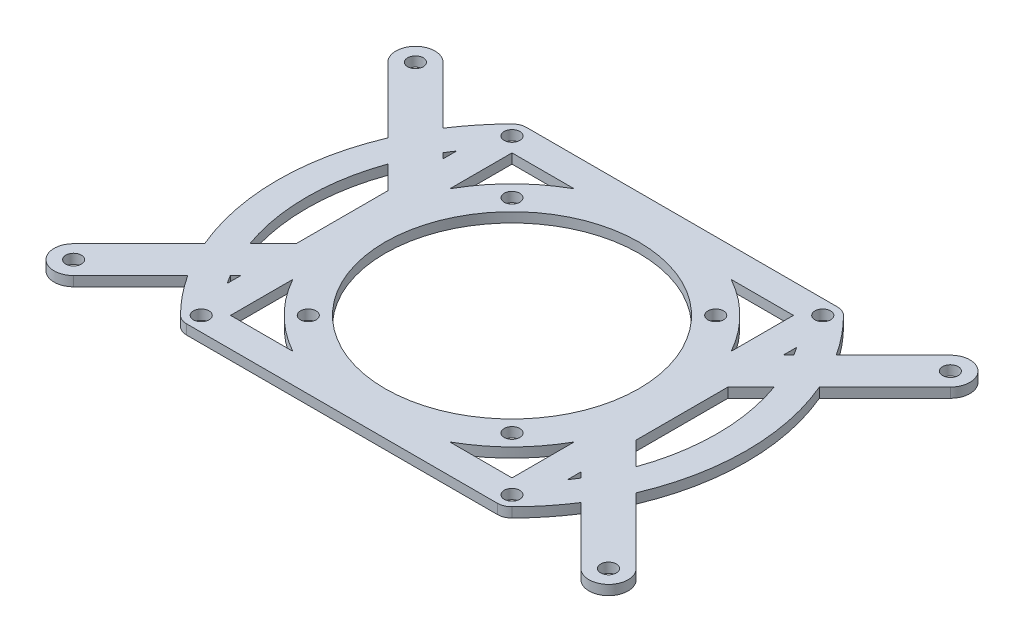
SolidWorks part; units mm, degrees
ref_plane "Front Plane" through (0, 0, 0) normal (0, 0, 1) x (1, 0, 0)
ref_plane "Top Plane" through (0, 0, 0) normal (0, 1, 0) x (1, 0, 0)
ref_plane "Right Plane" through (0, 0, 0) normal (1, 0, 0) x (0, 0, -1)
sketch "Sketch1" plane through (0, 0, 0) normal (0, 1, 0) x (1, 0, 0)
  line L1 (0, 4.2426) -> (-16.1407, 20.3833)
  line L3 (-51.9438, 37.8284) -> (-29.2993, 15.1839)
  line L4 (57.6006, 32.1716) -> (32.2808, 6.8518)
  line L5 (-57.6006, 32.1716) -> (-32.2808, 6.8518)
  line L6 (51.9438, 37.8284) -> (29.2993, 15.1839)
  line L7 (51.9438, -37.8284) -> (29.2993, -15.1839)
  line L8 (57.6006, -32.1716) -> (32.2808, -6.8518)
  line L9 (-57.6006, -32.1716) -> (-32.2808, -6.8518)
  line L10 (-51.9438, -37.8284) -> (-29.2993, -15.1839)
  line L11 (0, 4.2426) -> (16.1407, 20.3833)
  line L13 (0, -4.2426) -> (-16.1407, -20.3833)
  line L15 (0, -4.2426) -> (16.1407, -20.3833)
  line L16 (4.2426, 0) -> (20.3833, -16.1407)
  line L17 (-4.2426, 0) -> (-20.3833, -16.1407)
  line L18 (-4.2426, 0) -> (-20.3833, 16.1407)
  line L19 (4.2426, 0) -> (20.3833, 16.1407)
  circle A0 centre (54.7722, 35) radius 1.6
  arc A1 (57.6006, 32.1716) -> (51.9438, 37.8284) centre (54.7722, 35) ccw
  circle A2 centre (-54.7722, 35) radius 1.6
  arc A3 (-57.6006, 32.1716) -> (-51.9438, 37.8284) centre (-54.7722, 35) cw
  arc A4 (57.6006, -32.1716) -> (51.9438, -37.8284) centre (54.7722, -35) cw
  circle A5 centre (54.7722, -35) radius 1.6
  arc A6 (-57.6006, -32.1716) -> (-51.9438, -37.8284) centre (-54.7722, -35) ccw
  circle A7 centre (-54.7722, -35) radius 1.6
  arc A8 (-29.2993, -15.1839) -> (29.2993, -15.1839) centre (0, 0) ccw
  arc A9 (-20.3833, 16.1407) -> (-20.3833, -16.1407) centre (0, 0) ccw
  arc A11 (-32.2808, 6.8518) -> (-32.2808, -6.8518) centre (0, 0) ccw
  arc A12 (29.2993, 15.1839) -> (-29.2993, 15.1839) centre (0, 0) ccw
  arc A13 (32.2808, -6.8518) -> (32.2808, 6.8518) centre (0, 0) ccw
  circle A14 centre (20.8597, 20.8597) radius 1.6
  circle A15 centre (-20.8597, 20.8597) radius 1.6
  circle A16 centre (20.8597, -20.8597) radius 1.6
  circle A17 centre (-20.8597, -20.8597) radius 1.6
  arc A18 (16.1407, 20.3833) -> (-16.1407, 20.3833) centre (0, 0) ccw
  arc A19 (20.3833, -16.1407) -> (20.3833, 16.1407) centre (0, 0) ccw
  arc A20 (-16.1407, -20.3833) -> (16.1407, -20.3833) centre (0, 0) ccw
extrude "Boss-Extrude1" add sketch "Sketch1" along normal blind 2
sketch "Sketch2" plane through (0, 2, 0) normal (0, 1, 0) x (1, 0, 0)
  circle A0 centre (0, 0) radius 42
  circle A1 centre (0, 0) radius 48
  circle A3 centre (31.8198, 31.8198) radius 1.6
  circle A4 centre (-31.8198, 31.8198) radius 1.6
  circle A5 centre (31.8198, -31.8198) radius 1.6
  circle A6 centre (-31.8198, -31.8198) radius 1.6
extrude "Boss-Extrude2" add sketch "Sketch2" against normal up to surface (2 mm away) up to face at (-20.8597, 0, 22.4597)
sketch "Sketch3" plane through (0, 2, 0) normal (0, 1, 0) x (1, 0, 0)
  line L1 (34.8198, 31.8198) -> (34.8198, -31.8198)
  line L2 (-28.8198, -31.8198) -> (-28.8198, 31.8198)
  line L4 (-34.8198, 31.8198) -> (-34.8198, -31.8198)
  line L5 (28.8198, -31.8198) -> (28.8198, 31.8198)
  arc A0 (-34.8198, -31.8198) -> (-28.8198, -31.8198) centre (-31.8198, -31.8198) ccw
  arc A1 (-28.8198, 31.8198) -> (-34.8198, 31.8198) centre (-31.8198, 31.8198) ccw
  circle A2 centre (-31.8198, 31.8198) radius 1.6
  circle A3 centre (-31.8198, -31.8198) radius 1.6
  circle A4 centre (31.8198, -31.8198) radius 1.6
  circle A5 centre (31.8198, 31.8198) radius 1.6
  arc A6 (28.8198, 31.8198) -> (34.8198, 31.8198) centre (31.8198, 31.8198) cw
  arc A7 (34.8198, -31.8198) -> (28.8198, -31.8198) centre (31.8198, -31.8198) cw
extrude "Boss-Extrude3" add sketch "Sketch3" against normal up to surface (2 mm away) up to face at (-54.7722, 0, 36.6)
sketch "Sketch4" plane through (0, 2, 0) normal (0, 1, 0) x (1, 0, 0)
  line L0 (-28.8198, 31.8198) -> (-28.8198, 24.7402)
  line L1 (28.8198, -31.8198) -> (28.8198, -27.4437)
  line L2 (28.8198, 31.8198) -> (28.8198, 53.4887)
  line L3 (28.8198, 53.4887) -> (-28.8198, 53.4887)
  line L4 (-28.8198, 53.4887) -> (-28.8198, 31.8198)
  line L5 (-28.8198, -31.8198) -> (-28.8198, -57.6782)
  line L6 (-28.8198, -57.6782) -> (28.8198, -57.6782)
  line L7 (28.8198, -57.6782) -> (28.8198, -31.8198)
  line L8 (-28.8198, 24.7402) -> (0, 38.8462)
  line L9 (0, 38.8462) -> (28.8198, 24.7402)
  line L10 (-28.8198, -27.4437) -> (0, -37.5923)
  line L11 (0, -37.5923) -> (28.8198, -27.4437)
  line L12 (-28.8198, -27.4437) -> (-28.8198, -31.8198)
  line L13 (28.8198, 24.7402) -> (28.8198, 31.8198)
extrude "Cut-Extrude1" cut sketch "Sketch4" against normal blind 10
fillet "Fillet1" radius 3 4 edges at (-28.8198, 1, -38.3851) (28.8198, 1, -38.3851) (28.8198, 1, 38.3851) (-28.8198, 1, 38.3851)
sketch "Sketch5" plane through (0, 2, 0) normal (0, 1, 0) x (1, 0, 0)
  line L0 (-31.8198, 34.8198) -> (31.8198, 34.8198)
  line L2 (0, 28.8198) -> (28.8198, 28.8198)
  line L3 (28.8198, 31.8198) -> (28.8198, 16.0754) construction
  line L4 (28.8198, 28.8198) -> (28.8198, 31.8198)
  line L5 (28.8198, 31.8198) -> (29.7534, 32.7534)
  line L6 (29.7534, 32.7534) -> (31.8198, 34.8198)
  line L7 (0, 28.8198) -> (-28.8198, 28.8198)
  line L8 (-28.8198, 16.0754) -> (-28.8198, 31.8198) construction
  line L9 (-28.8198, 28.8198) -> (-28.8198, 31.8198)
  line L10 (-28.8198, 31.8198) -> (-31.8198, 34.8198)
  line L12 (-28.8198, -31.8198) -> (-31.8198, -34.8198)
  line L13 (-28.8198, -28.8198) -> (-28.8198, -31.8198)
  line L14 (0, -28.8198) -> (-28.8198, -28.8198)
  line L15 (29.7534, -32.7534) -> (31.8198, -34.8198)
  line L16 (28.8198, -31.8198) -> (29.7534, -32.7534)
  line L17 (28.8198, -28.8198) -> (28.8198, -31.8198)
  line L18 (0, -28.8198) -> (28.8198, -28.8198)
  line L20 (-31.8198, -34.8198) -> (31.8198, -34.8198)
  arc A0 (-28.8198, 31.8198) -> (-33.9411, 33.9411) centre (-31.8198, 31.8198) ccw construction
  arc A1 (33.9411, 33.9411) -> (28.8198, 31.8198) centre (31.8198, 31.8198) ccw construction
extrude "Boss-Extrude4" add sketch "Sketch5" against normal up to surface (2 mm away) up to face at (0, 0, 0)
sketch "Sketch6" plane through (0, 2, 0) normal (0, 1, 0) x (1, 0, 0)
  circle A0 centre (0, 0) radius 26
extrude "Cut-Extrude2" cut sketch "Sketch6" against normal blind 10
